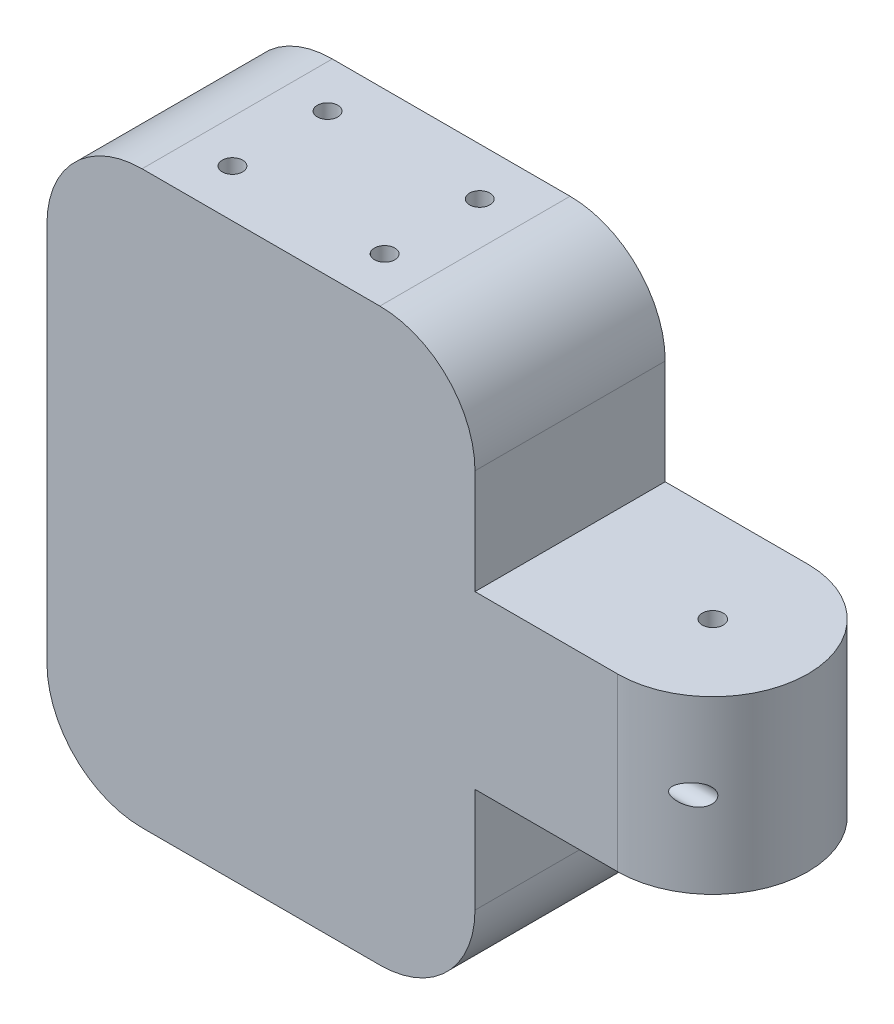
SolidWorks part; units mm, degrees
ref_plane "Front Plane" through (0, 0, 0) normal (0, 0, 1) x (1, 0, 0)
ref_plane "Top Plane" through (0, 0, 0) normal (0, 1, 0) x (1, 0, 0)
ref_plane "Right Plane" through (0, 0, 0) normal (1, 0, 0) x (0, 0, -1)
sketch "Sketch1" plane through (0, 0, 0) normal (0, 1, 0) x (1, 0, 0)
  line L0 (15, 20) -> (0, 20)
  line L2 (0, 0) -> (15, 0)
  line L5 (0, 20) -> (0, 0)
  circle A0 centre (15, 10) radius 1.1
  arc A2 (15, 0) -> (15, 20) centre (15, 10) ccw
  dimension "D3" = 2.2
  dimension "D1" = 20
  dimension "D2" = 15
extrude "hinge" add sketch "Sketch1" along normal mid plane 18
ref_point "Point1"
sketch "Sketch3" plane through (0, 0, 0) normal (-1, 0, 0) x (0, 0, 1)
  line L0 (0, 9) -> (0, -9) construction
  line L1 (-20, -30) -> (0, -30)
  line L2 (-20, -30) -> (-20, 30)
  line L3 (-20, 30) -> (0, 30)
  line L4 (0, -30) -> (0, 30)
  line L5 (-20, -30) -> (0, 30) construction
  line L6 (-20, 30) -> (0, -30) construction
  point P0 (-10, 0)
  dimension "D1" = 60
extrude "thumb_flap" add sketch "Sketch3" along normal blind 45
ref_plane "Plane1" through (50, 0, 0) normal (1, 0, 0) x (0, 0, -1)
sketch "Sketch4" plane through (50, 0, 0) normal (1, 0, 0) x (0, 0, -1)
  line L0 (0, 9) -> (0, -9) construction
  line L1 (0, 9) -> (0, -9)
  circle A0 centre (2.1, 0) radius 1.1
  point P4 (0, 0)
  dimension "D1" = 2.2
  dimension "D2" = 2.1
extrude "tendon_path" cut sketch "Sketch4" against normal through all both and the other way through all contours A0 region at (50, 0, -2.1)
sketch "Sketch5" plane through (0, 30, 0) normal (0, 1, 0) x (1, 0, 0)
  line L0 (-45, 20) -> (0, 0) construction
  line L1 (-22.5, 10) -> (-22.5, 20) construction
  line L2 (-45, 20) -> (0, 20) construction
  line L3 (-22.5, 10) -> (0, 10) construction
  circle A0 centre (-30.5, 15) radius 1.075
  circle A1 centre (-14.5, 15) radius 1.075
  circle A2 centre (-14.5, 5) radius 1.075
  circle A3 centre (-30.5, 5) radius 1.075
  point P4 (-22.5, 10)
  dimension "D1" = 2.15
  dimension "D2" = 8
  dimension "D3" = 5
extrude "m2_pins" cut sketch "Sketch5" against normal blind 4.2 and the other way through all
fillet "Fillet1" radius 10 4 edges at (0, 30, -10) (-45, 30, -10) (0, -30, -10) (-45, -30, -10)
